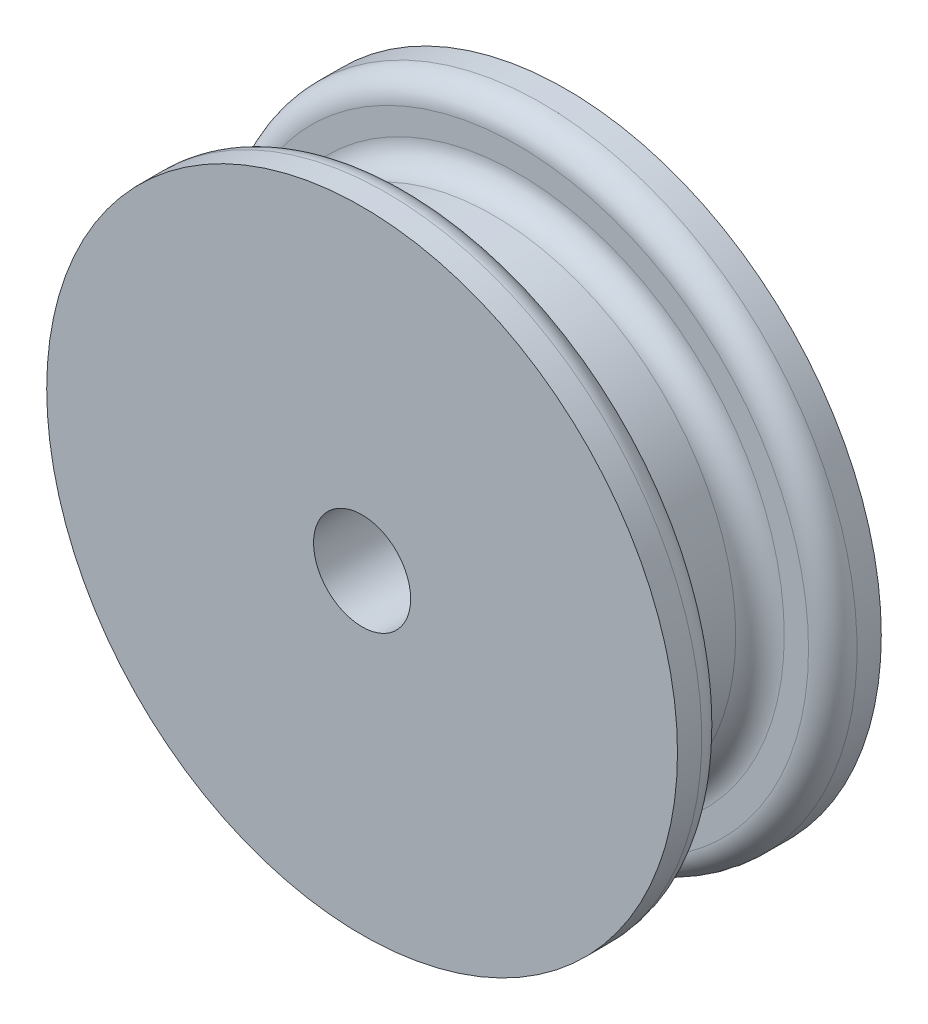
SolidWorks part; units mm, degrees
ref_plane "Front Plane" through (0, 0, 0) normal (0, 0, 1) x (1, 0, 0)
ref_plane "Top Plane" through (0, 0, 0) normal (0, 1, 0) x (1, 0, 0)
ref_plane "Right Plane" through (0, 0, 0) normal (1, 0, 0) x (0, 0, -1)
sketch "Sketch1" plane through (0, 0, 0) normal (0, 0, 1) x (1, 0, 0)
  circle A0 centre (0, 0) radius 6.5
  circle A1 centre (0, 0) radius 1
  dimension "D1" = 13
  dimension "D2" = 2
extrude "Boss-Extrude1" add sketch "Sketch1" along normal blind 4.2
sketch "Sketch2" plane through (0, 0, 0) normal (1, 0, 0) x (0, 0, -1)
  line L0 (-4.2, 6.5) -> (-3.7, 6.5)
  line L1 (-3.2, 6) -> (-3.2, 5.5)
  line L2 (-2.7, 5) -> (-1.5, 5)
  line L3 (-1, 5.5) -> (-1, 6)
  line L4 (-0.5, 6.5) -> (0, 6.5)
  line L5 (-4.2, 6.5) -> (-4.2, 7.642)
  line L6 (-4.2, 7.642) -> (0, 7.642)
  line L7 (0, 7.642) -> (0, 6.5)
  arc A0 (-1, 6) -> (-0.5, 6.5) centre (-0.5, 6) cw
  arc A1 (-3.7, 6.5) -> (-3.2, 6) centre (-3.7, 6) cw
  arc A2 (-1.5, 5) -> (-1, 5.5) centre (-1.5, 5.5) ccw
  arc A3 (-3.2, 5.5) -> (-2.7, 5) centre (-2.7, 5.5) ccw
  point P11 (-1, 6.5)
  point P14 (-3.2, 6.5)
  dimension "D4" = 0.5
  dimension "D1" = 5
  dimension "D2" = 1
  dimension "D3" = 1
sketch "Sketch3" plane through (0, 0, 0) normal (1, 0, 0) x (0, 0, -1)
  line L0 (0, 0) -> (-9.8056, 0) construction
revolve "Cut-Revolve1" cut sketch "Sketch2" angle 360 about L0
